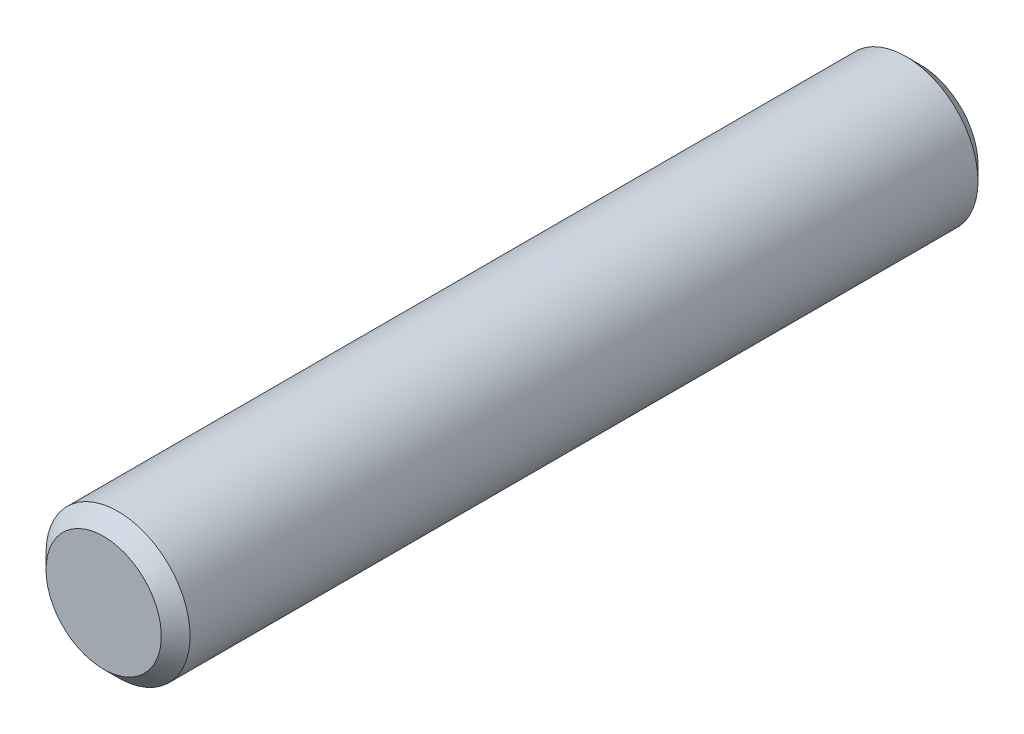
SolidWorks part; units mm, degrees
ref_plane "Front" through (0, 0, 0) normal (0, 0, 1) x (1, 0, 0)
ref_plane "Top" through (0, 0, 0) normal (0, 1, 0) x (1, 0, 0)
ref_plane "Right" through (0, 0, 0) normal (1, 0, 0) x (0, 0, -1)
sketch "Sketch1" plane through (0, 0, 0) normal (0, 0, 1) x (1, 0, 0)
  circle A0 centre (0, 0) radius 7.9375
  dimension "Diameter" = 15.875
sketch "Sketch2" plane through (0, 0, 0) normal (1, 0, 0) x (0, 0, -1)
  line L0 (-45, 0) -> (45, 0) construction
  line L1 (5.8, 7.9375) -> (5.8, -7.9375) construction
  line L2 (8.7312, 0) -> (-8.7312, 0) construction
  line L3 (-5.8, 7.9375) -> (-5.8, -7.9375) construction
  line L4 (-45, 7.9375) -> (-45, -7.9375) construction
  line L5 (45, 7.9375) -> (45, -7.9375) construction
  point P3 (5.8, 0)
  point P8 (0, 0)
  point P9 (-5.8, 0)
  point P15 (-45, 0)
  point P18 (45, 0)
  dimension "D1" = 15.875
  dimension "Length" = 90
  dimension "D2" = 50.8
  dimension "D3" = 50.8
sketch "Sketch3" plane through (0, 0, 0) normal (0, 0, 1) x (1, 0, 0)
  circle A0 centre (0, 0) radius 7.9375
  dimension "D1" = 15.875
extrude "Boss-Extrude1" add sketch "Sketch3" along normal mid plane 90
chamfer "Chamfer1" distance 1.5875 angle 45 2 edges at (7.9375, 0, -45) (7.9375, 0, 45)
equation "\"D1@Sketch3\" = \"Diameter@Sketch1\""
equation "\"D1@Boss-Extrude1\" = \"Length@Sketch2\""
equation "\"D1@Chamfer1\" = \"Diameter@Sketch1\" * .1"
equation "\"D1@Sketch2\" = \"Diameter@Sketch1\""
